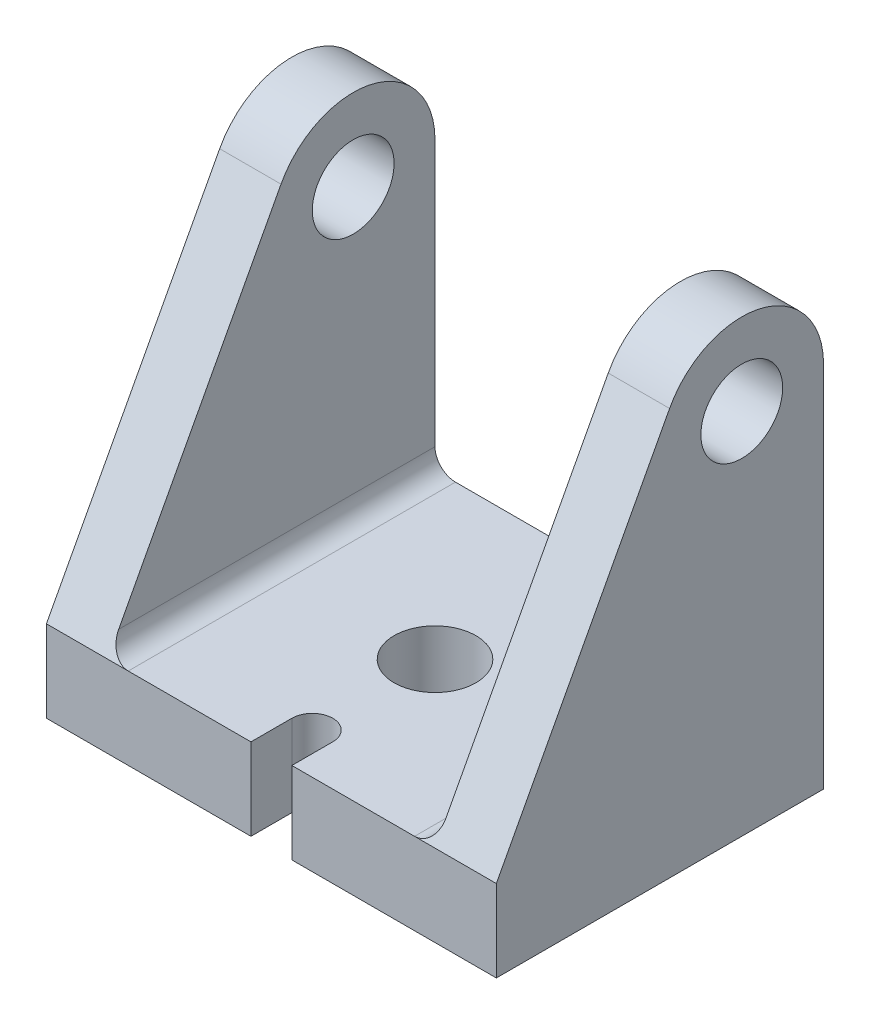
SolidWorks part; units mm, degrees
material "Leaded Commercial Bronze"
ref_plane "Front Plane" through (0, 0, 0) normal (0, 0, 1) x (1, 0, 0)
ref_plane "Top Plane" through (0, 0, 0) normal (0, 1, 0) x (1, 0, 0)
ref_plane "Right Plane" through (0, 0, 0) normal (1, 0, 0) x (0, 0, -1)
sketch "Sketch1" plane through (0, 0, 0) normal (0, 1, 0) x (1, 0, 0)
  line L0 (-34.925, -25.4) -> (34.925, 25.4) construction
  line L1 (-34.925, 25.4) -> (34.925, 25.4)
  line L2 (-34.925, 25.4) -> (-34.925, -25.4)
  line L3 (-34.925, -25.4) -> (34.925, -25.4)
  line L4 (34.925, 25.4) -> (34.925, -25.4)
  dimension "D1" = 69.85
  dimension "D2" = 50.8
extrude "Boss-Extrude1" add sketch "Sketch1" along normal blind 12.7
sketch "Sketch2" plane through (0, 0, 0) normal (1, 0, 0) x (0, 0, -1)
  line L1 (-25.4, 12.7) -> (1.4941, 63.1265)
  line L2 (-25.4, 12.7) -> (25.4, 12.7)
  line L3 (25.4, 12.7) -> (25.4, 57.15)
  line L4 (27.94, 0) -> (-27.94, 0) construction
  arc A0 (1.4941, 63.1265) -> (25.4, 57.15) centre (12.7, 57.15) cw
  circle A1 centre (12.7, 57.15) radius 6.35
  point P8 (0, 0)
  point P10 (0, 0)
  point P13 (0, 0)
  dimension "D1" = 12.7
  dimension "D2" = 12.7
  dimension "D3" = 57.15
extrude "Boss-Extrude2" add sketch "Sketch2" against normal blind 9.525 from surface starting at face at (34.925, 6.35, 0)
extrude "Boss-Extrude3" add sketch "Sketch2<2>" along normal blind 9.525 from surface starting at face at (-34.925, 6.35, 0)
sketch "Sketch2<2>" plane through (0, 0, 0) normal (1, 0, 0) x (0, 0, -1) same geometry as "Sketch2"
sketch "Sketch3" plane through (0, 12.7, 0) normal (0, 1, 0) x (1, 0, 0)
  line L0 (0, -27.94) -> (0, 27.94) construction
  line L1 (3.175, -19.05) -> (3.175, -25.4)
  line L2 (-25.4, -25.4) -> (25.4, -25.4) construction
  line L3 (-3.175, -19.05) -> (-3.175, -25.4)
  line L4 (-3.175, -25.4) -> (3.175, -25.4)
  circle A0 centre (0, 0) radius 6.35
  arc A1 (3.175, -19.05) -> (-3.175, -19.05) centre (0, -19.05) ccw
  dimension "D1" = 12.7
  dimension "D2" = 6.35
  dimension "D3" = 19.05
extrude "Cut-Extrude1" cut sketch "Sketch3" against normal through all
fillet "Fillet2" radius 3.175 2 edges at (25.4, 12.7, 0) (-25.4, 12.7, 0)
